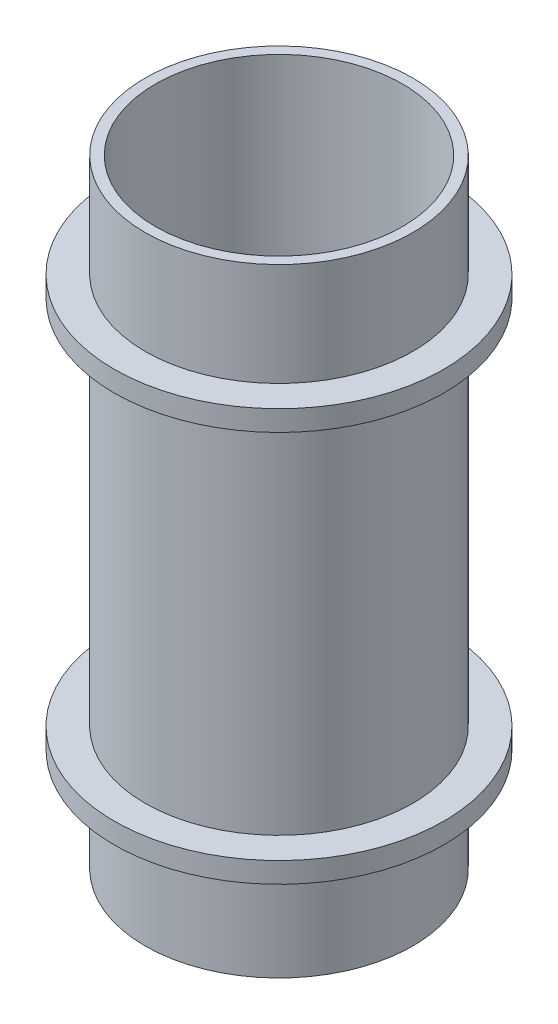
SolidWorks part; units mm, degrees
ref_plane "Спереди" through (0, 0, 0) normal (0, 0, 1) x (1, 0, 0)
ref_plane "Сверху" through (0, 0, 0) normal (0, 1, 0) x (1, 0, 0)
ref_plane "Справа" through (0, 0, 0) normal (1, 0, 0) x (0, 0, -1)
other "Центр тяжести"
sketch "Эскиз1" plane through (0, 0, 0) normal (0, 1, 0) x (1, 0, 0)
  circle A0 centre (0, 0) radius 12
  circle A1 centre (0, 0) radius 13
  dimension "D1" = 24
  dimension "D2" = 26
extrude "Бобышка-Вытянуть1" add sketch "Эскиз1" along normal blind 60
sketch "Эскиз2" plane through (0, 60, 0) normal (0, 1, 0) x (1, 0, 0)
  circle A1 centre (0, 0) radius 16
  circle A3 centre (0, 0) radius 12
  dimension "D1" = 32
  dimension "D2" = 24
extrude "Бобышка-Вытянуть3" add sketch "Эскиз2" against normal blind 2 from offset 10 offset against normal yes
sketch "Эскиз3" plane through (0, 0, 0) normal (0, -1, 0) x (1, 0, 0)
  circle A0 centre (0, 0) radius 12
  circle A1 centre (0, 0) radius 16
  dimension "D1" = 24
extrude "Бобышка-Вытянуть4" add sketch "Эскиз3" against normal blind 2 from offset 10 offset against normal yes
